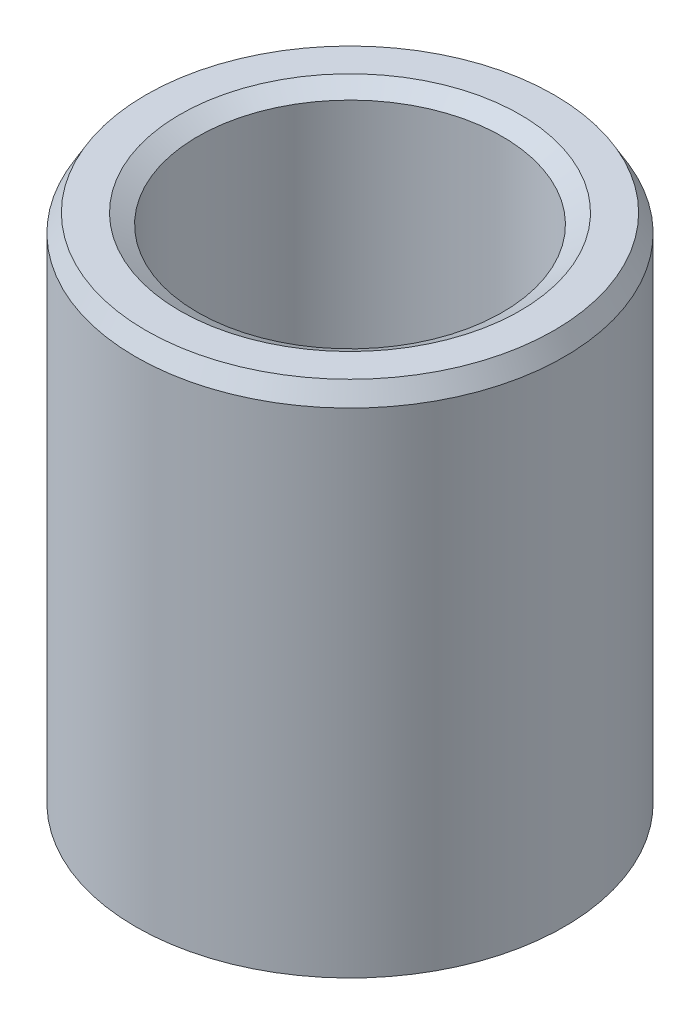
SolidWorks part; units mm, degrees
ref_plane "Front Plane" through (0, 0, 0) normal (0, 0, 1) x (1, 0, 0)
ref_plane "Top Plane" through (0, 0, 0) normal (0, 1, 0) x (1, 0, 0)
ref_plane "Right Plane" through (0, 0, 0) normal (1, 0, 0) x (0, 0, -1)
sketch "Sketch1" plane through (0, 0, 0) normal (0, 1, 0) x (1, 0, 0)
  circle A0 centre (0, 0) radius 42.5
  dimension "SLEEVE_OD" = 85
extrude "Boss-Extrude1" add sketch "Sketch1" along normal blind 103.4103
sketch "Sketch2" plane through (0, 0, 0) normal (0, 1, 0) x (1, 0, 0)
  circle A0 centre (0, 0) radius 30.2092
  dimension "BORE_D" = 60.4185
extrude "Cut-Extrude1" cut sketch "Sketch2" along normal through all
chamfer "Chamfer1" distance 3.5144 angle 30 4 edges at (0, 103.4103, 30.2092) (0, 0, 30.2092) (0, 0, 42.5) (0, 103.4103, 42.5) first distance on face at (0, 103.4103, 30.2092) first distance on face at (0, 0, 30.2092) first distance on face at (0, 103.4103, 42.5)
